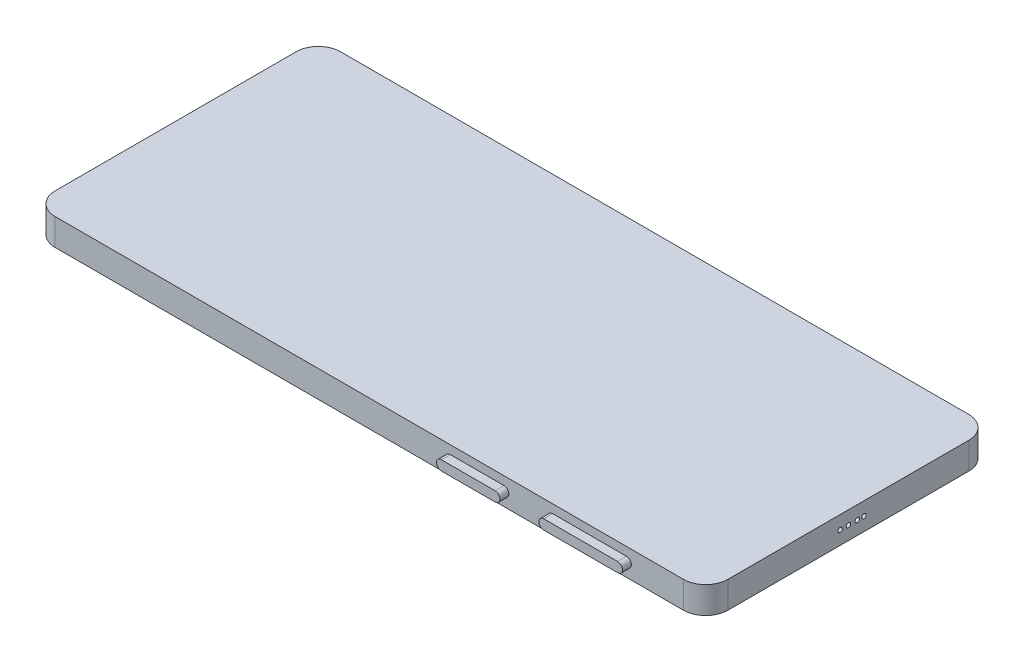
SolidWorks part; units mm, degrees
ref_plane "前视基准面" through (0, 0, 0) normal (0, 0, 1) x (1, 0, 0)
ref_plane "上视基准面" through (0, 0, 0) normal (0, 1, 0) x (1, 0, 0)
ref_plane "右视基准面" through (0, 0, 0) normal (1, 0, 0) x (0, 0, -1)
other "Configuration Table"
sketch "草图1" plane through (0, 0, 0) normal (0, 1, 0) x (1, 0, 0)
  line L1 (-60.4264, 29.9625) -> (90.2635, 29.9625)
  line L2 (-60.4264, 29.9625) -> (-60.4264, -33.9742)
  line L3 (-60.4264, -33.9742) -> (90.2635, -33.9742)
  line L4 (90.2635, 29.9625) -> (90.2635, -33.9742)
extrude "凸台-拉伸1" add sketch "草图1" along normal blind 6
fillet "圆角6" radius 5 1 edges at (90.2635, 3, -29.9625)
fillet "圆角7" radius 5 1 edges at (90.2635, 3, 33.9742)
fillet "圆角8" radius 5 1 edges at (-60.4264, 3, 33.9742)
fillet "圆角9" radius 5 1 edges at (-60.4264, 3, -29.9625)
sketch "草图2" plane through (-60.4264, 0, 0) normal (-1, 0, 0) x (0, 0, 1)
  line L1 (-2.4486, 3.9405) -> (5.4859, 3.9405)
  line L2 (-2.4486, 3.9405) -> (-2.4486, 2.1309)
  line L3 (-2.4486, 2.1309) -> (5.4859, 2.1309)
  line L4 (5.4859, 3.9405) -> (5.4859, 2.1309)
extrude "切除-拉伸1" cut sketch "草图2" against normal blind 11
sketch "草图3" plane through (-49.4264, 0, 0) normal (-1, 0, 0) x (0, 0, 1)
  line L1 (-1.7643, 3.4175) -> (5.0267, 3.4175)
  line L2 (-1.7643, 3.4175) -> (-1.7643, 2.9605)
  line L3 (-1.7643, 2.9605) -> (5.0267, 2.9605)
  line L4 (5.0267, 3.4175) -> (5.0267, 2.9605)
extrude "凸台-拉伸4" add sketch "草图3" along normal blind 10
sketch "草图4" plane through (-60.4264, 0, 0) normal (-1, 0, 0) x (0, 0, 1)
  circle A0 centre (13.0724, 3.1105) radius 1
  circle A1 centre (16.0652, 3.1105) radius 1
  circle A2 centre (19.4061, 3.1105) radius 1
  circle A3 centre (22.4685, 3.1105) radius 1
  circle A4 centre (10.0796, 3.1105) radius 1
  circle A5 centre (25.3917, 3.1105) radius 1
extrude "切除-拉伸2" cut sketch "草图4" against normal blind 10
sketch "草图7" plane through (-50.4264, 0, 0) normal (-1, 0, 0) x (0, 0, 1)
  line L0 (-21.8672, 3.1105) -> (-5.5806, 3.1105) construction
  line L1 (-21.8672, 4.1607) -> (-5.5806, 4.1607)
  line L2 (-21.8672, 2.0604) -> (-5.5806, 2.0604)
  arc A0 (-21.8672, 4.1607) -> (-21.8672, 2.0604) centre (-21.8672, 3.1105) ccw
  arc A1 (-5.5806, 2.0604) -> (-5.5806, 4.1607) centre (-5.5806, 3.1105) ccw
  circle A2 centre (-21.8672, 3.1105) radius 0.6264
  point P3 (-13.7239, 3.1105)
extrude "凸台-拉伸5" add sketch "草图7" along normal blind 5.8871
sketch "草图9" plane through (-60.4264, 0, 0) normal (-1, 0, 0) x (0, 0, 1)
  line L0 (-22.7721, 3.4175) -> (-8.2255, 3.4175) construction
  line L1 (-22.7721, 4.3572) -> (-8.2255, 4.3572)
  line L2 (-22.7721, 2.4778) -> (-8.2255, 2.4778)
  arc A0 (-22.7721, 4.3572) -> (-22.7721, 2.4778) centre (-22.7721, 3.4175) ccw
  arc A1 (-8.2255, 2.4778) -> (-8.2255, 4.3572) centre (-8.2255, 3.4175) ccw
  point P2 (-15.4988, 3.4175)
sketch "草图11" plane through (-60.4264, 0, 0) normal (-1, 0, 0) x (0, 0, 1)
  circle A0 centre (-22.7721, 3.4175) radius 0.5
extrude "切除-拉伸4" cut sketch "草图11" against normal blind 10
sketch "草图12" plane through (0, 0, 0) normal (0, -1, 0) x (1, 0, 0)
  circle A0 centre (58.8951, 2.0059) radius 23.4422
extrude "凸台-拉伸6" add sketch "草图12" along normal blind 3
fillet "圆角11" radius 5 1 edges at (58.8951, -3, -21.4364)
sketch "草图13" plane through (0, -3, 0) normal (0, -1, 0) x (1, 0, 0)
  circle A0 centre (69.3275, 0) radius 7.5449
sketch "草图14" plane through (0, -3, 0) normal (0, -1, 0) x (1, 0, 0)
  circle A0 centre (52.7962, 11.395) radius 5.3449
  circle A1 centre (52.7962, -5.492) radius 5.3449
sketch "草图15" plane through (0, 0, 33.9742) normal (0, 0, 1) x (1, 0, 0)
  line L0 (72.5375, 3) -> (56.0061, 3) construction
  line L1 (72.5375, 1.9073) -> (56.0061, 1.9073)
  line L2 (72.5375, 4.0927) -> (56.0061, 4.0927)
  line L3 (45.0922, 3) -> (33.0549, 3) construction
  line L4 (45.0922, 1.9073) -> (33.0549, 1.9073)
  line L5 (45.0922, 4.0927) -> (33.0549, 4.0927)
  arc A0 (72.5375, 1.9073) -> (72.5375, 4.0927) centre (72.5375, 3) ccw
  arc A1 (56.0061, 4.0927) -> (56.0061, 1.9073) centre (56.0061, 3) ccw
  arc A2 (45.0922, 1.9073) -> (45.0922, 4.0927) centre (45.0922, 3) ccw
  arc A3 (33.0549, 4.0927) -> (33.0549, 1.9073) centre (33.0549, 3) ccw
  point P2 (64.2718, 3)
  point P7 (39.0736, 3)
extrude "凸台-拉伸7" add sketch "草图15" along normal blind 2
sketch "草图16" plane through (90.2635, 0, 0) normal (1, 0, 0) x (0, 0, -1)
  circle A0 centre (0, 3) radius 0.5
  circle A1 centre (1.4888, 3) radius 0.5
  circle A2 centre (-2.0059, 3) radius 0.5
  circle A3 centre (-3.8486, 3) radius 0.5
extrude "切除-拉伸5" cut sketch "草图16" against normal blind 7
